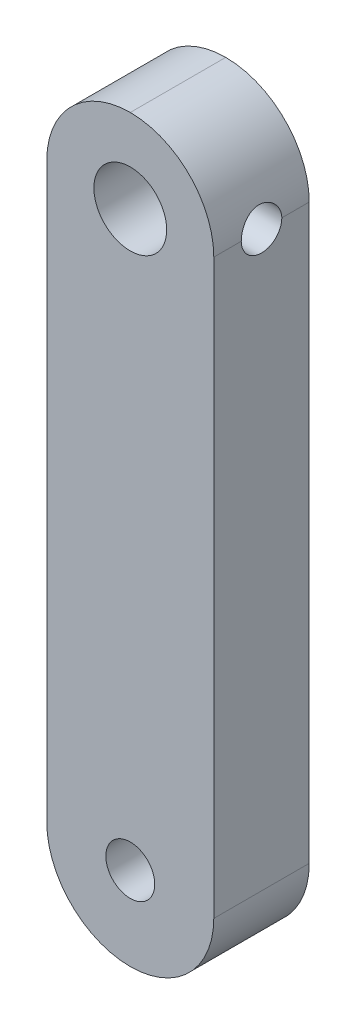
SolidWorks part; units mm, degrees
ref_plane "Plan de face" through (0, 0, 0) normal (0, 0, 1) x (1, 0, 0)
ref_plane "Plan de dessus" through (0, 0, 0) normal (0, 1, 0) x (1, 0, 0)
ref_plane "Plan de droite" through (0, 0, 0) normal (1, 0, 0) x (0, 0, -1)
sketch "Esquisse2" plane through (0, 0, 0) normal (0, 0, 1) x (1, 0, 0)
  line L1 (0, 0) -> (14, 0)
  line L2 (0, 0) -> (0, 62)
  line L3 (0, 62) -> (14, 62)
  line L4 (14, 0) -> (14, 62)
  dimension "D1" = 14
  dimension "D2" = 62
extrude "Boss.-Extru.1" add sketch "Esquisse2" along normal blind 8
sketch "Esquisse3" plane through (0, 0, 8) normal (0, 0, 1) x (1, 0, 0)
  line L0 (7, 0) -> (7, 62) construction
  line L1 (0, 0) -> (14, 0) construction
  line L2 (14, 62) -> (0, 62) construction
  line L3 (0, 31) -> (14, 31) construction
  line L4 (0, 62) -> (0, 0) construction
  line L5 (14, 0) -> (14, 62) construction
  circle A0 centre (7, 55) radius 3.05
  circle A1 centre (7, 7) radius 2.05
  dimension "D1" = 7
  dimension "D2" = 6.1
  dimension "D3" = 4.1
extrude "Enlèv. mat.-Extru.1" cut sketch "Esquisse3" against normal through all both and the other way through all
fillet "Congé1" radius 7 4 edges at (14, 0, 4) (0, 0, 4) (0, 62, 4) (14, 62, 4)
sketch "Esquisse4" plane through (14, 0, 0) normal (1, 0, 0) x (0, 0, -1)
  line L0 (-4, 0) -> (-4, 62) construction
  line L1 (-8, 0) -> (0, 0) construction
  line L2 (-8, 62) -> (0, 62) construction
  line L3 (-8, 58.05) -> (0, 51.95) construction
  circle A0 centre (-4, 55) radius 1.7
  dimension "D1" = 3.4
extrude "Enlèv. mat.-Extru.2" cut sketch "Esquisse4" against normal up to next
